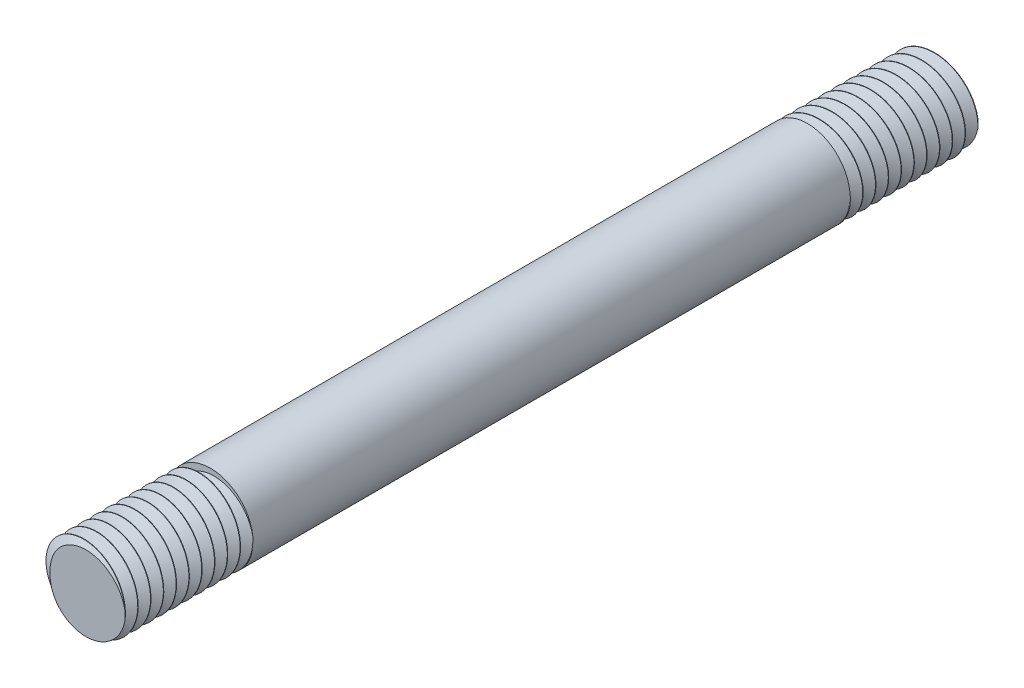
SolidWorks part; units mm, degrees
ref_plane "Alzado" through (0, 0, 0) normal (0, 0, 1) x (1, 0, 0)
ref_plane "Planta" through (0, 0, 0) normal (0, 1, 0) x (1, 0, 0)
ref_plane "Vista lateral" through (0, 0, 0) normal (1, 0, 0) x (0, 0, -1)
sketch "Croquis1" plane through (0, 0, 0) normal (0, 0, 1) x (1, 0, 0)
  circle A0 centre (0, 0) radius 5
  dimension "D1" = 10
extrude "Saliente-Extruir1" add sketch "Croquis1" along normal blind 15
sketch "Croquis2" plane through (0, 0, 0) normal (0, 0, -1) x (-1, 0, 0)
  circle A0 centre (0, 0) radius 5 construction
  circle A1 centre (0, 0) radius 5
curve "Hélice/Espiral1" pitch 1.5 height 18.375 turns 12.25
sketch "Croquis3" plane through (0, 0, 0) normal (0, 1, 0) x (1, 0, 0)
  line L0 (-5, -0.725) -> (-5, 0.725)
  line L1 (-5, 0.725) -> (-3.8748, 0.0753)
  line L2 (-3.8748, -0.0753) -> (-5, -0.725)
  line L3 (-3.7443, 0) -> (-5, 0) construction
  arc A0 (-3.8748, -0.0753) -> (-3.8748, 0.0753) centre (-3.9183, 0) ccw
  dimension "D2" = 0.087
  dimension "D1" = 60
  dimension "D3" = 1.45
sweep "Cortar-Barrer1" cut profiles "Croquis3" path "Hélice/Espiral1" align with end faces yes
sketch "Croquis4" plane through (0, 0, 15) normal (0, 0, 1) x (1, 0, 0)
  circle A0 centre (0, 0) radius 5
  dimension "D1" = 10
extrude "Saliente-Extruir2" add sketch "Croquis4" along normal blind 35
mirror "Simetría2" about plane through (0, 0, 50) normal (0, 0, 1) of bodies 103
